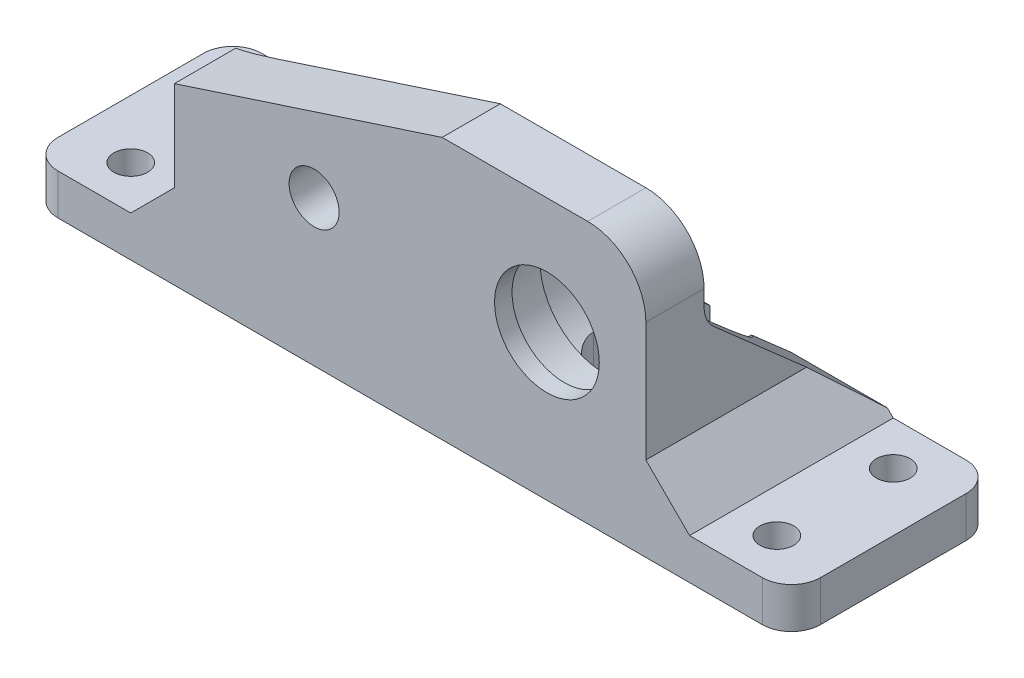
SolidWorks part; units mm, degrees
ref_plane "Front Plane" through (0, 0, 0) normal (0, 0, 1) x (1, 0, 0)
ref_plane "Top Plane" through (0, 0, 0) normal (0, 1, 0) x (1, 0, 0)
ref_plane "Right Plane" through (0, 0, 0) normal (1, 0, 0) x (0, 0, -1)
sketch "Sketch1" plane through (0, 0, 0) normal (0, 0, 1) x (1, 0, 0)
  line L0 (7, 20) -> (-18, 20)
  line L2 (-64, -25) -> (17, -25)
  line L3 (17, 10) -> (17, -25)
  line L4 (-18, 20) -> (-64, 5)
  line L5 (-64, 5) -> (-64, -25)
  circle A0 centre (0, 0) radius 9
  circle A1 centre (-40, 0) radius 4.3
  arc A2 (7, 20) -> (17, 10) centre (7, 10) cw
  dimension "D2" = 18
  dimension "D3" = 8.6
  dimension "D7" = 20
  dimension "D8" = 18
  dimension "D10" = 10
  dimension "D1" = 40
  dimension "D4" = 25
  dimension "D5" = 24
  dimension "D6" = 17
  dimension "D9" = 30
extrude "Boss-Extrude1" add sketch "Sketch1" along normal blind 10
sketch "Sketch3" plane through (-64, 0, 0) normal (-1, 0, 0) x (0, 0, 1)
  line L0 (0, -25) -> (-25, -25)
  line L1 (-25, -25) -> (-25, -17)
  line L2 (-25, -17) -> (0, 5)
  line L3 (0, 5) -> (0, -25)
  dimension "D1" = 25
  dimension "D2" = 8
extrude "Boss-Extrude2" add sketch "Sketch3" against normal blind 10
sketch "Sketch4" plane through (17, 0, 0) normal (1, 0, 0) x (0, 0, -1)
  line L4 (0, 5) -> (0, -25)
  line L5 (0, -25) -> (25, -25)
  line L6 (25, -25) -> (25, -17)
  line L7 (25, -17) -> (0, 5)
  line L8 (0, 5) -> (0, -25)
  line L9 (0, -25) -> (25, -25)
  line L10 (25, -25) -> (25, -17)
  line L11 (25, -17) -> (0, 5)
  dimension "D1" = 0
extrude "Boss-Extrude3" add sketch "Sketch4" against normal blind 10
sketch "Sketch5" plane through (0, 0, 0) normal (1, 0, 0) x (0, 0, -1)
  line L5 (25, -17) -> (0, 5)
  line L6 (25, -25) -> (25, -17)
  line L7 (0, -25) -> (25, -25)
  line L8 (0, -5.6569) -> (0, -25)
  line L9 (0, 5) -> (0, -5.6569)
  line L10 (25, -17) -> (0, 5)
  line L11 (25, -25) -> (25, -17)
  line L12 (0, -25) -> (25, -25)
  line L13 (0, -5.6569) -> (0, -25)
  line L14 (0, 5) -> (0, -5.6569)
  dimension "D1" = 0
extrude "Boss-Extrude4" add sketch "Sketch5" against normal blind 10 from offset 7 offset against normal yes
sketch "Sketch2" plane through (0, 0, 0) normal (0, 0, -1) x (-1, 0, 0)
  circle A0 centre (0, 0) radius 11.2
  dimension "D1" = 22.4
extrude "Cut-Extrude1" cut sketch "Sketch2" against normal blind 7 and the other way through all
fillet "Fillet1" radius 5 7 edges at (-59, 5, 0) (13.511, 5, 0) (7, -16.8715, 0) (-17, -10, 0) (-13.511, 5, 0) (-7, -16.8715, 0)
sketch "Sketch8" plane through (0, 0, -25) normal (0, 0, -1) x (-1, 0, 0)
  circle A0 centre (0, 0) radius 13
  dimension "D1" = 26
extrude "Cut-Extrude4" cut sketch "Sketch8" against normal up to surface (25 mm away) up to face at (-35.7, 0, 0)
sketch "Sketch9" plane through (0, -25, 0) normal (0, -1, 0) x (1, 0, 0)
  line L0 (-64, 10) -> (17, 10) construction
  line L1 (17, -25) -> (42, -25)
  line L2 (17, -25) -> (17, 10)
  line L3 (17, 10) -> (42, 10)
  line L4 (42, -25) -> (42, 10)
  line L5 (-64, -25) -> (-89, -25)
  line L6 (-64, -25) -> (-64, 10)
  line L7 (-64, 10) -> (-89, 10)
  line L8 (-89, -25) -> (-89, 10)
  line L10 (-54, -25) -> (-64, -25) construction
  line L11 (7, -25) -> (17, -25) construction
  line L12 (-17, -25) -> (-7, -25) construction
  line L13 (-17, -25) -> (-54, -25)
  line L14 (-17, -25) -> (-17, 10)
  line L15 (-17, 10) -> (-54, 10)
  line L16 (-54, -25) -> (-54, 10)
  dimension "D1" = 35
  dimension "D2" = 25
extrude "Boss-Extrude5" add sketch "Sketch9" against normal blind 7
fillet "Fillet2" radius 5 4 edges at (42, -21.5, -25) (42, -21.5, 10) (-89, -21.5, 10) (-89, -21.5, -25)
hole_wizard "M5 Clearance Hole1" positions "Sketch11" profile "Sketch10" hole size "M5" standard "ANSI Metric" end condition through all
sketch "Sketch11" plane through (0, -18, 0) normal (0, 1, 0) x (1, 0, 0)
  line L0 (-79, 17.5) -> (32, 17.5) construction
  line L1 (32, 17.5) -> (32, -2.5) construction
  line L2 (32, -2.5) -> (-79, -2.5) construction
  line L3 (-79, -2.5) -> (-79, 17.5) construction
  line L5 (-89, -5) -> (-89, 20) construction
  line L6 (42, 20) -> (42, -5) construction
  line L7 (-84, 25) -> (-64, 25) construction
  line L8 (-64, -10) -> (-84, -10) construction
  point P0 (-79, 17.5)
  point P2 (-79, -2.5)
  point P4 (32, 17.5)
  point P6 (32, -2.5)
  point P33 (-25.5, 17.5)
  dimension "D1" = 20
  dimension "D2" = 10
  dimension "D3" = 10
  dimension "D4" = 7.5
  dimension "D5" = 7.5
  dimension "D6" = 57.5
  dimension "D7" = 111
sketch "Sketch10" plane through (-79, -18, -17.5) normal (1, 0, 0) x (0, 0, 1)
  line L0 (0, 0) -> (0, 7)
  line L1 (0, 7) -> (2.9, 7)
  line L2 (2.9, 7) -> (2.9, 0)
  line L5 (2.9, 0) -> (0, 0)
  line L11 (0, -6.35) -> (0, 107.95) construction
  dimension "Thru Hole Dia." = 5.8
  dimension "Thru Hole Depth" = 7
sketch "Sketch13" plane through (0, 0, -25) normal (0, 0, -1) x (-1, 0, 0)
  line L0 (-17, -18) -> (-24.5, -18)
  line L1 (-17, -18) -> (-37, -18) construction
  line L2 (-24.5, -18) -> (-17, -10.5)
  line L3 (-17, -10.5) -> (-17, -18)
  line L4 (64, -18) -> (71.5, -18)
  line L5 (84, -18) -> (64, -18) construction
  line L6 (71.5, -18) -> (64, -10.5)
  line L7 (64, -10.5) -> (64, -18)
  dimension "D1" = 7.5
  dimension "D2" = 7.5
extrude "Boss-Extrude6" add sketch "Sketch13" against normal up to surface (35 mm away) up to face at (-18.6929, -5.3429, 10)
sketch "Sketch14" plane through (17, 0, 0) normal (-1, 0, 0) x (0, 0, 1)
  line L0 (-25, -17) -> (-25, -10.5)
  line L1 (-25, -10.5) -> (-17.6136, -10.5)
  line L2 (-17.6136, -10.5) -> (-25, -17)
extrude "Cut-Extrude5" cut sketch "Sketch14" against normal through all and the other way through all
